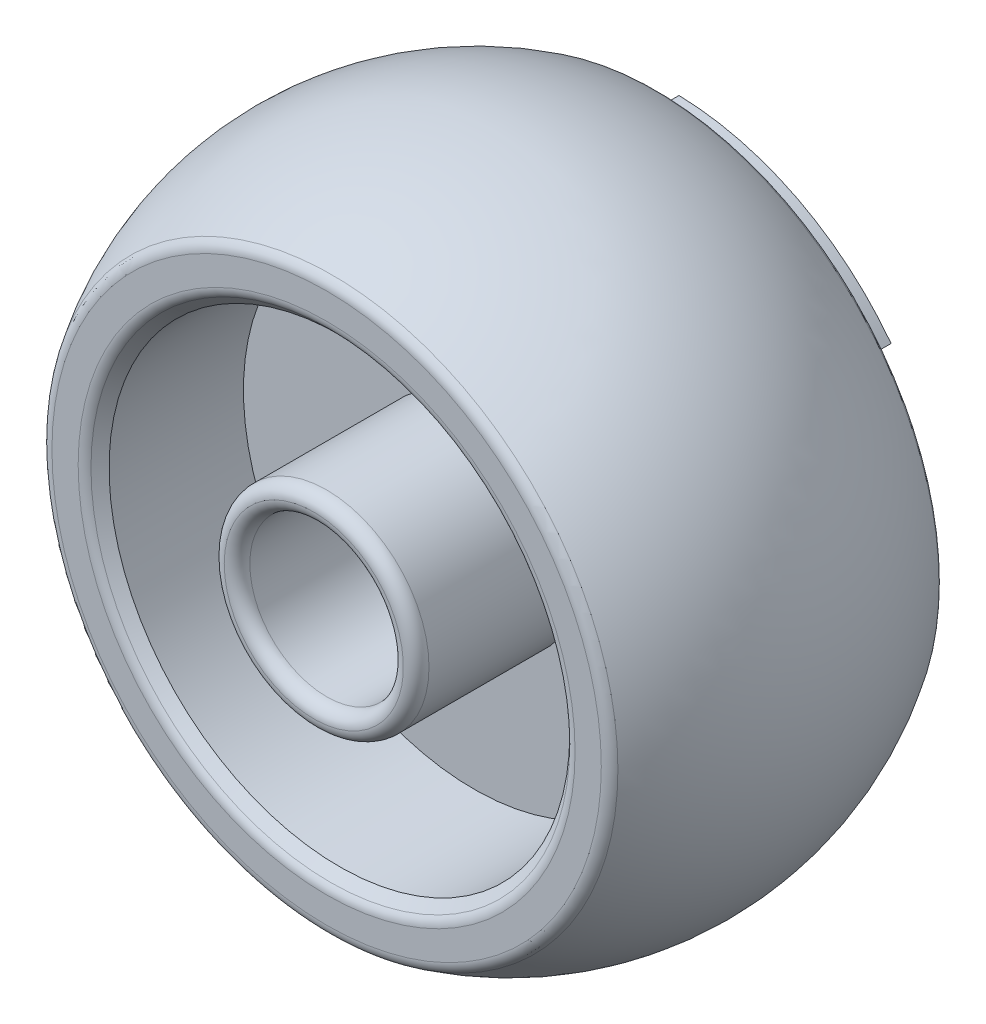
SolidWorks part; units mm, degrees
material "Nylon 101"
ref_plane "Plan de face" through (0, 0, 0) normal (0, 0, 1) x (1, 0, 0)
ref_plane "Plan de dessus" through (0, 0, 0) normal (0, 1, 0) x (1, 0, 0)
ref_plane "Plan de droite" through (0, 0, 0) normal (1, 0, 0) x (0, 0, -1)
sketch "Esquisse1" plane through (0, 0, 0) normal (1, 0, 0) x (0, 0, -1)
  line L0 (-4.7147, 0) -> (4.792, 0) construction
  line L1 (7, 3) -> (-7, 3)
  line L2 (-7, 3) -> (-7, 4)
  line L3 (-7, 4) -> (-0.75, 4)
  line L4 (-0.75, 4) -> (-0.75, 9)
  line L5 (-0.75, 9) -> (-6, 9)
  line L6 (-6.5, 9.5) -> (-6.5, 11)
  line L7 (0, -13.8929) -> (0, 13.236) construction
  line L8 (6.5, 9.5) -> (6.5, 11)
  line L9 (0.75, 9) -> (6, 9)
  line L10 (0.75, 4) -> (0.75, 9)
  line L11 (7, 4) -> (0.75, 4)
  line L12 (7, 3) -> (7, 4)
  line L13 (-6, 9) -> (-6.5, 9.5)
  line L14 (6, 9) -> (6.5, 9.5)
  arc A0 (6.5, 11) -> (-6.5, 11) centre (0, 1.4375) ccw
  point P9 (-6.5, 9)
  point P14 (-0.75, 6.5)
  point P16 (6.5, 9)
  point P22 (0, 3)
  point P26 (0, 13)
  dimension "D8" = 13
  dimension "D1" = 3
  dimension "D2" = 4
  dimension "D3" = 9
  dimension "D4" = 2
  dimension "D5" = 6.5
  dimension "D6" = 7
  dimension "D7" = 1.5
revolve "Révolution1" add sketch "Esquisse1" angle 360 about L0
fillet "Fillet1" radius 0.5 2 edges at (3, 0, -7) (4, 0, -7)
fillet "Fillet2" radius 0.5 2 edges at (4, 0, 7) (3, 0, 7)
fillet "Fillet3" radius 0.5 2 edges at (11, 0, 6.5) (9.5, 0, 6.5)
fillet "Fillet4" radius 0.5 2 edges at (9.5, 0, -6.5) (11, 0, -6.5)
scale "Scale1" bodies to scale 101 scale about centroid uniform scaling yes scale factor 2
sketch "Sketch1" plane through (0, 0, -13) normal (0, 0, -1) x (-1, 0, 0)
  line L0 (-15.4755, 11.7227) -> (-17.1087, 12.9598)
  line L1 (-0.4837, 19.4082) -> (-0.5347, 21.4564)
  line L7 (14.8724, 12.479) -> (16.4419, 13.7959) [skipped]
  line L8 (19.0292, -3.8472) -> (21.0374, -4.2532) [skipped]
  line L9 (8.8567, -17.2763) -> (9.7913, -19.0995) [skipped]
  line L10 (-18.814, -4.7903) -> (-20.7994, -5.2958) [skipped]
  line L11 (-7.9851, -17.696) -> (-8.8278, -19.5635) [skipped]
  line L12 (17.8899, 7.5408) -> (19.7778, 8.3367)
  line L13 (17.0498, -9.2852) -> (18.8491, -10.2651)
  line L14 (-2.4144, -19.2635) -> (-2.6692, -21.2964)
  line L15 (-16.5661, -10.123) -> (-18.3144, -11.1913)
  arc A0 (-0.5347, 21.4564) -> (-17.1087, 12.9598) centre (0, 0) ccw
  arc A1 (-0.4837, 19.4082) -> (-15.4755, 11.7227) centre (0, 0) ccw
  arc A6 (18.8491, -10.2651) -> (19.7778, 8.3367) centre (0, 0) ccw
  arc A7 (17.0498, -9.2852) -> (17.8899, 7.5408) centre (0, 0) ccw
  arc A8 (-18.3144, -11.1913) -> (-2.6692, -21.2964) centre (0, 0) ccw
  arc A9 (-16.5661, -10.123) -> (-2.4144, -19.2635) centre (0, 0) ccw
  dimension "D1" = 7
  dimension "D2" = 3
extrude "Boss-Extrude1" add sketch "Sketch1" along normal blind 1
sketch "Sketch2" plane through (0, 0, 0) normal (0, 1, 0) x (1, 0, 0)
  point P0 (0, 0)
  point P1 (0, 0)
  point P5 (0, 0)
